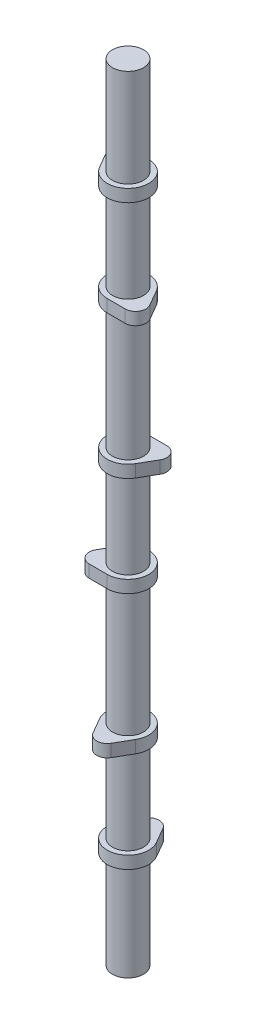
SolidWorks part; units mm, degrees
ref_plane "Front Plane" through (0, 0, 0) normal (0, 0, 1) x (1, 0, 0)
ref_plane "Top Plane" through (0, 0, 0) normal (0, 1, 0) x (1, 0, 0)
ref_plane "Right Plane" through (0, 0, 0) normal (1, 0, 0) x (0, 0, -1)
sketch "Sketch1" plane through (0, 0, 0) normal (0, 1, 0) x (1, 0, 0)
  line L0 (-5.4993, 15.875) -> (-10.9985, 6.35)
  line L1 (5.4993, 15.875) -> (10.9985, 6.35)
  arc A0 (-10.9985, 6.35) -> (10.9985, 6.35) centre (0, 0) ccw
  arc A1 (5.4993, 15.875) -> (-5.4993, 15.875) centre (0, 12.7) ccw
  dimension "D1" = 12.7
  dimension "D2" = 12.7
  dimension "D3" = 25.4
extrude "Boss-Extrude1" add sketch "Sketch1" along normal mid plane 7.62
ref_axis "Axis1" through (0, 18.4652, 0) along (0, -1, 0)
pattern_linear "LPattern1" count 2 spacing 60.96 along (0, 1, 0) of "Boss-Extrude1"
move or copy body "Body-Move/Copy1" bodies to move or copy 102 copy no rotation origin (0, 0, 0) rotation axis (0, 1, 0) rotation angle 180
pattern_linear "LPattern2" count 3 spacing 146.05 along (0, 1, 0) of bodies 101 103
move or copy body "Body-Move/Copy2" bodies to move or copy 106 104 copy no rotation origin (0, 0, 0) rotation axis (0, 1, 0) rotation angle 120
move or copy body "Body-Move/Copy3" bodies to move or copy 107 105 copy no rotation origin (0, 0, 0) rotation axis (0, -1, 0) rotation angle 120
sketch "Sketch2" plane through (0, 0, 0) normal (0, 1, 0) x (1, 0, 0)
  circle A0 centre (0, 0) radius 9.5
  dimension "D1" = 19
extrude "Boss-Extrude2" add sketch "Sketch2" along normal blind 480.06 from offset 63.5 offset against normal yes
combine bodies "Combine1" operation type add bodies to combine 103 108 109 110 111 112
